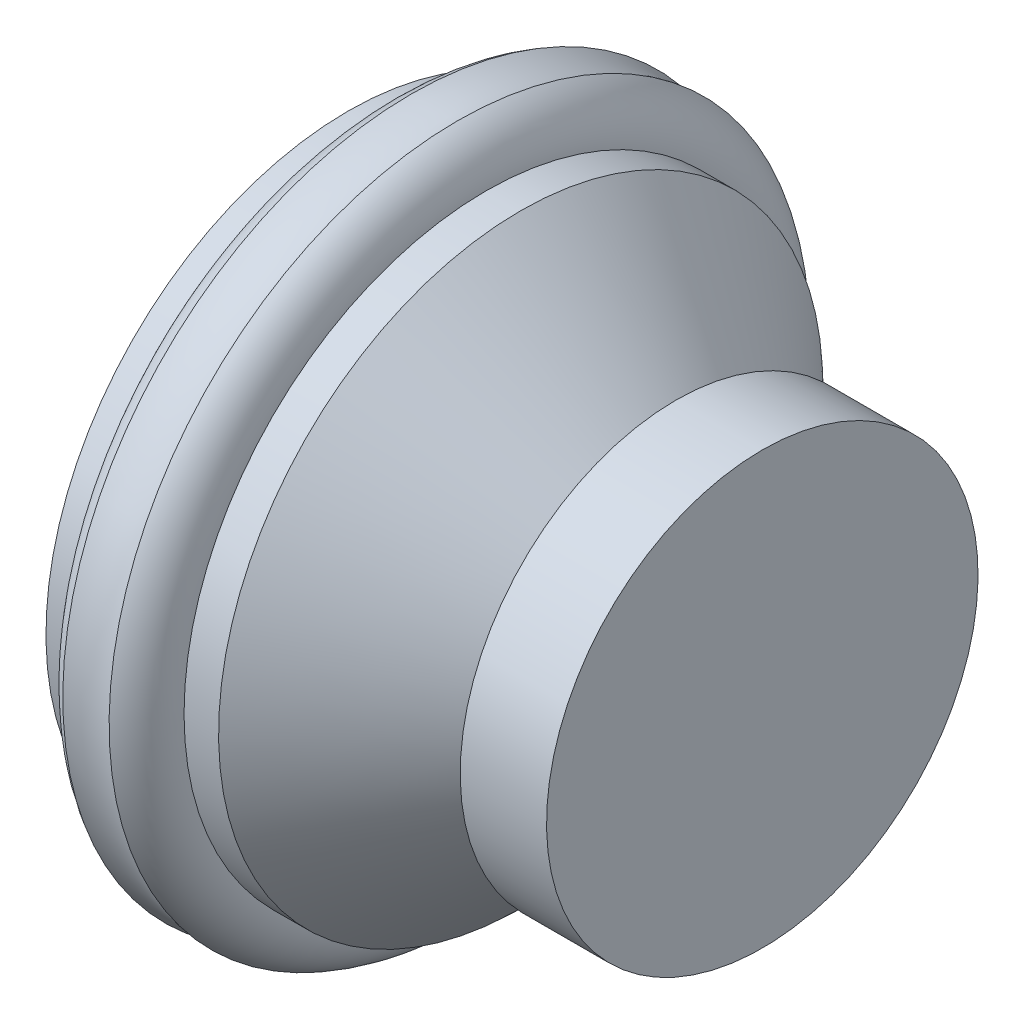
SolidWorks part; units mm, degrees
ref_plane "Front Plane" through (0, 0, 0) normal (0, 0, 1) x (1, 0, 0)
ref_plane "Top Plane" through (0, 0, 0) normal (0, 1, 0) x (1, 0, 0)
ref_plane "Right Plane" through (0, 0, 0) normal (1, 0, 0) x (0, 0, -1)
sketch "Sketch1" plane through (0, 0, 0) normal (0, 0, 1) x (1, 0, 0)
  line L0 (-119, 0) -> (-143, 0) construction
  line L1 (143, -52.5) -> (-143, -52.5) construction
  line L2 (143, -52.5) -> (143, 52.5) construction
  line L3 (143, 52.5) -> (-143, 52.5) construction
  line L4 (-143, -52.5) -> (-143, 52.5) construction
  line L5 (143, -52.5) -> (-143, 52.5) construction
  line L6 (143, 52.5) -> (-143, -52.5) construction
  line L7 (143, 52.5) -> (-119, 52.5) construction
  line L8 (143, 52.5) -> (143, -52.5) construction
  line L9 (143, -52.5) -> (-119, -52.5) construction
  line L10 (-119, 52.5) -> (-119, -52.5) construction
  line L11 (143, 52.5) -> (-119, -52.5) construction
  line L12 (143, -52.5) -> (-119, 52.5) construction
  line L13 (-119, -52.5) -> (-143, -52.5) construction
  line L14 (-119, -52.5) -> (-119, -47.5) construction
  line L15 (-119, -47.5) -> (-143, -47.5) construction
  line L16 (-143, -52.5) -> (-143, -47.5) construction
  line L17 (-119, -52.5) -> (-143, -47.5) construction
  line L18 (-119, -47.5) -> (-143, -52.5) construction
  line L19 (-119, 17.5) -> (-143, 17.5) construction
  line L20 (-119, 17.5) -> (-119, -17.5) construction
  line L21 (-119, -17.5) -> (-143, -17.5) construction
  line L22 (-143, 17.5) -> (-143, -17.5) construction
  line L23 (-119, 17.5) -> (-143, -17.5) construction
  line L24 (-119, -17.5) -> (-143, 17.5) construction
  line L25 (-119, 0) -> (-119, 12.5) construction
  line L26 (-133, 17.5) -> (-143, 17.5)
  line L27 (-119, 17.5) -> (-119, 0)
  line L28 (-119, 0) -> (-143, 0)
  line L29 (-143, 17.5) -> (-143, 0)
  line L30 (-119, 17.5) -> (-143, 0) construction
  line L31 (-119, 0) -> (-143, 17.5) construction
  line L32 (-143, 17.5) -> (-133, 17.5) construction
  line L33 (-119, 12.5) -> (-124, 12.5)
  line L34 (-119, 12.5) -> (-119, 0)
  line L35 (-119, 0) -> (-124, 0)
  line L36 (-124, 12.5) -> (-124, 9)
  line L37 (-119, 12.5) -> (-124, 0) construction
  line L38 (-119, 0) -> (-124, 12.5) construction
  line L39 (-124, 0) -> (-124, 9) construction
  line L40 (-124, 9) -> (-133, 17.5)
  line L41 (-124, 3.6458) -> (-124, 0)
  point P0 (0, 0)
  point P8 (12, 0)
  point P11 (-131, -50)
  point P16 (-131, 0)
  point P20 (-131, 8.75)
  point P23 (-121.5, 6.25)
  dimension "D1" = 262
  dimension "D2" = 286
  dimension "D3" = 105
  dimension "D4" = 5
  dimension "D5" = 35
  dimension "D6" = 35
  dimension "D7" = 12.5
  dimension "D8" = 5
  dimension "D9" = 10
  dimension "D10" = 9
revolve "Revolve2" add sketch "Sketch1" angle 360 about L28
sketch "Sketch2" plane through (0, 0, 0) normal (0, 0, 1) x (1, 0, 0)
  line L0 (-133, 17.5) -> (-143, 17.5) construction
  line L1 (-119, 0) -> (-143, 0) construction
  line L2 (-119, -12.5) -> (-119, 12.5) construction
  line L3 (-143, 17.5) -> (-143, -17.5) construction
  line L4 (-135, 17.5) -> (-141, 17.5)
  line L5 (-138, 17.5) -> (-138, 25) construction
  arc A0 (-135, 17.5) -> (-141, 17.5) centre (-138, 17.5) ccw
  arc A1 (-136.6585, 20.1833) -> (-139.3415, 20.1833) centre (-138, 25) cw
  point P8 (-138, 29.7352)
  point P15 (-137.9306, 21.4522)
  point P16 (0, 0)
  point P17 (0, 0)
  point P18 (-138, 24.9529)
  dimension "D2" = 3
  dimension "D3" = 5
  dimension "D1" = 5
  dimension "D4" = 7.5
revolve "Revolve3" add sketch "Sketch2" angle 360 about L1 region at (-138, 18.6735, 0)
